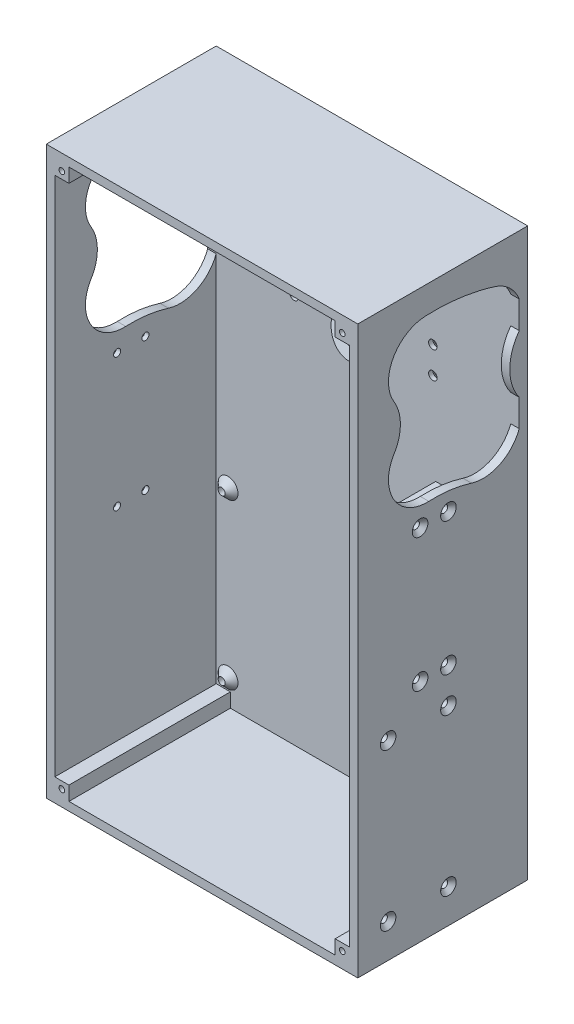
SolidWorks part; units mm, degrees
ref_plane "Płaszczyzna przednia" through (0, 0, 0) normal (0, 0, 1) x (1, 0, 0)
ref_plane "Płaszczyzna górna" through (0, 0, 0) normal (0, 1, 0) x (1, 0, 0)
ref_plane "Płaszczyzna prawa" through (0, 0, 0) normal (1, 0, 0) x (0, 0, -1)
sketch "Szkic1" plane through (0, 0, 0) normal (0, 1, 0) x (1, 0, 0)
  line L1 (0, 0) -> (110, 0)
  line L2 (0, 0) -> (0, 60)
  line L3 (0, 60) -> (110, 60)
  line L4 (110, 0) -> (110, 60)
  dimension "D1" = 110
  dimension "D2" = 60
extrude "Dodanie-wyciągnięcie1" add sketch "Szkic1" along normal blind 200
shell "Skorupa1" thickness 3 removed face at (55, 100, 0)
sketch "Szkic8" plane through (0, 0, -57) normal (0, 0, 1) x (1, 0, 0)
  line L0 (3, 197) -> (3, 192) construction
  line L1 (3, 197) -> (3, 3) construction
  line L2 (107, 197) -> (3, 197) construction
  line L3 (3, 192) -> (8, 192)
  line L4 (3, 192) -> (3, 197)
  line L5 (3, 197) -> (8, 197)
  line L6 (8, 192) -> (8, 197)
  circle A0 centre (5.5, 194.5) radius 1
  dimension "D2" = 2
  dimension "D1" = 5
sketch "Szkic12" plane through (0, 0, -57) normal (0, 0, 1) x (1, 0, 0)
  line L1 (107, 197) -> (102, 197)
  line L2 (107, 197) -> (107, 192)
  line L3 (107, 192) -> (102, 192)
  line L4 (102, 197) -> (102, 192)
  circle A0 centre (104.5, 194.5) radius 1
  dimension "D3" = 2
  dimension "D1" = 5
  dimension "D2" = 5
  dimension "D4" = 2.5
  dimension "D5" = 2.5
sketch "Szkic14" plane through (0, 0, -57) normal (0, 0, 1) x (1, 0, 0)
  line L1 (107, 3) -> (102, 3)
  line L2 (107, 3) -> (107, 8)
  line L3 (107, 8) -> (102, 8)
  line L4 (102, 3) -> (102, 8)
  circle A0 centre (104.5, 5.5) radius 1
  dimension "D2" = 2
  dimension "D3" = 2.5
  dimension "D1" = 5
  dimension "D4" = 2.5
sketch "Szkic16" plane through (0, 0, -57) normal (0, 0, 1) x (1, 0, 0)
  line L1 (3, 3) -> (8, 3)
  line L2 (3, 3) -> (3, 8)
  line L3 (3, 8) -> (8, 8)
  line L4 (8, 3) -> (8, 8)
  circle A0 centre (5.5, 5.5) radius 1
  dimension "D2" = 2
  dimension "D1" = 5
extrude "Dodanie-wyciągnięcie11" add sketch "Szkic16" along normal blind 57
extrude "Dodanie-wyciągnięcie14" add sketch "Szkic8" along normal blind 57
extrude "Dodanie-wyciągnięcie16" add sketch "Szkic12" along normal blind 57
extrude "Dodanie-wyciągnięcie17" add sketch "Szkic14" along normal blind 57
sketch "Szkic17" plane through (107, -8.5912, 0.3025) normal (-1, 0, 0) x (0, 0, 1)
  line L0 (-38.6312, 60.9912) -> (-38.6312, 16.5912) construction
  line L1 (-57.3012, 109.5912) -> (-38.6312, 109.5912)
  line L2 (-57.3012, 109.5912) -> (-57.3012, 117.1912)
  line L3 (-57.3012, 117.1912) -> (-38.6312, 117.1912)
  line L4 (-38.6312, 109.5912) -> (-38.6312, 117.1912)
  line L5 (-0.3025, 16.5912) -> (-57.3025, 16.5912) construction
  line L6 (-38.6312, 109.5912) -> (-38.6312, 16.5912) construction
  line L7 (-57.3012, 68.5912) -> (-38.6312, 68.5912)
  line L8 (-57.3012, 68.5912) -> (-57.3012, 60.9912)
  line L9 (-57.3012, 60.9912) -> (-38.6312, 60.9912)
  line L10 (-38.6312, 68.5912) -> (-38.6312, 60.9912)
  dimension "D1" = 18.67
  dimension "D2" = 7.6
  dimension "D3" = 44.4
  dimension "D4" = 93
  dimension "D5" = 18.67
  dimension "D6" = 7.6
extrude "Dodanie-wyciągnięcie18" add sketch "Szkic17" along normal blind 26.5
sketch "Szkic18" plane through (80.5, 0, 0) normal (-1, 0, 0) x (0, 0, 1)
  line L1 (-56.9987, 108.6) -> (-56.9987, 101) construction
  line L2 (-38.3287, 101) -> (-38.3287, 108.6) construction
  line L3 (-38.3287, 108.6) -> (-56.9987, 108.6) construction
  circle A0 centre (-42.3287, 105.6) radius 1.5
  circle A1 centre (-51.9787, 105.6) radius 1.5
  dimension "D1" = 3
  dimension "D2" = 3
  dimension "D3" = 3
  dimension "D4" = 5.02
  dimension "D5" = 3
  dimension "D6" = 4
extrude "Wytnij-wyciągnięcie2" cut sketch "Szkic18" against normal blind 5
sketch "Szkic19" plane through (80.5, 0, 0) normal (-1, 0, 0) x (0, 0, 1)
  line L0 (-56.9987, 52.4) -> (-38.3287, 52.4) construction
  line L4 (-38.3287, 52.4) -> (-38.3287, 60) construction
  line L5 (-56.9987, 60) -> (-56.9987, 52.4) construction
  circle A0 centre (-42.3287, 55.4) radius 1.5
  circle A1 centre (-51.9787, 55.4) radius 1.5
  dimension "D1" = 3
  dimension "D2" = 3
  dimension "D3" = 3
  dimension "D4" = 4
  dimension "D5" = 3
  dimension "D6" = 5.02
extrude "Wytnij-wyciągnięcie3" cut sketch "Szkic19" against normal blind 5
sketch "Szkic21" plane through (110, 0, 0) normal (1, 0, 0) x (0, 0, -1)
  line L0 (0, 0) -> (22, 0) construction
  line L1 (0, 0) -> (60, 0) construction
  line L2 (0, 0) -> (31, 0) construction
  line L5 (22, 126.68) -> (32, 126.68) construction
  line L7 (22, 126.68) -> (22, 79.68) construction
  line L8 (32, 126.68) -> (32, 79.68) construction
  line L9 (22, 79.68) -> (22, 0) construction
  line L10 (22, 79.68) -> (0, 79.68) construction
  line L11 (0, 200) -> (0, 0) construction
  circle A0 centre (22, 79.68) radius 1.25
  circle A1 centre (32, 79.68) radius 1.25
  circle A2 centre (22, 126.68) radius 1.25
  circle A3 centre (32, 126.68) radius 1.25
  dimension "D4" = 2.5
  dimension "D5" = 2.5
  dimension "D7" = 2.5
  dimension "D8" = 2.5
  dimension "D1" = 10
  dimension "D2" = 10
  dimension "D3" = 47
  dimension "D6" = 79.68
  dimension "D9" = 22
extrude "Wytnij-wyciągnięcie4" cut sketch "Szkic21" against normal blind 125
chamfer "Sfazowanie3" distance 1.5 angle 45 8 edges at (0, 79.68, -23.25) (0, 79.68, -33.25) (0, 126.68, -33.25) (0, 126.68, -23.25) (110, 126.68, -23.25) (110, 126.68, -33.25) (110, 79.68, -33.25) (110, 79.68, -23.25)
sketch "Szkic22" plane through (0, 108.6, 0) normal (0, 1, 0) x (1, 0, 0)
  line L0 (80.5, 38.3287) -> (98, 38.3287)
  line L1 (80.5, 38.3287) -> (107, 38.3287) construction
  line L2 (107, 38.3287) -> (107, 53.3287)
  line L3 (107, 38.3287) -> (107, 56.9987) construction
  line L4 (98, 38.3287) -> (107, 53.3287)
  line L5 (98, 38.3287) -> (107, 38.3287)
  dimension "D1" = 17.5
  dimension "D2" = 15
extrude "Wytnij-wyciągnięcie5" cut sketch "Szkic22" against normal blind 10 contours L5 L2 L4
sketch "Szkic24" plane through (0, 0, -57) normal (0, 0, 1) x (1, 0, 0)
  line L0 (8, 197) -> (102, 197) construction
  line L1 (55, 197) -> (55, 174.23) construction
  line L2 (55, 174.23) -> (55, 179.73) construction
  line L8 (55, 174.23) -> (48.524, 174.23) construction
  arc A2 (61.476, 174.23) -> (48.524, 174.23) centre (55, 179.73) ccw
  spline S0 degree 2 poles (48.524, 174.23) (55, 174.198) (61.476, 174.23) knots 0 0 0 1 1 1
  dimension "D3" = 16.9928
  dimension "D1" = 22.77
sketch "Szkic43" plane through (107, 0, 0) normal (-1, 0, 0) x (0, 0, 1)
  line L0 (-57, 139.4863) -> (-57, 149.0844)
  line L1 (-57, 179.13) -> (-57, 169.4506)
  line L2 (-57, 192) -> (-57, 8) construction
  line L4 (-57, 192) -> (-57, 179.13) construction
  arc A0 (-57, 179.13) -> (-48.3123, 187.2414) centre (-44.2889, 174.224) cw
  arc A2 (-23.8685, 190.4648) -> (-12.8025, 169.7853) centre (-24.4601, 176.8476) cw
  arc A3 (-12.8025, 169.7853) -> (-13.3589, 154.7507) centre (0.4315, 161.7679) ccw
  arc A4 (-13.3589, 154.7507) -> (-25.0675, 133.2257) centre (-24.4599, 146.8422) cw
  arc A5 (-25.0675, 133.2257) -> (-40.1456, 131.2527) centre (-27.0175, 89.5268) ccw
  arc A6 (-40.1456, 131.2527) -> (-57, 139.4863) centre (-44.2348, 144.2496) cw
  arc A7 (-57, 149.0844) -> (-57, 169.4506) centre (-70.8555, 159.2675) ccw
  spline S0 degree 2 poles (-48.3123, 187.2414) (-36.3724, 190.9917) (-23.8685, 190.4648) knots 0 0 0 1 1 1
  dimension "D2" = 13.63
  dimension "D3" = 13.63
  dimension "D4" = 15.4731
  dimension "D1" = 12.87
extrude "Wytnij-wyciągnięcie10" cut sketch "Szkic43" against normal blind 3 and the other way blind 125
sketch "Szkic48" plane through (0, 0, -57) normal (0, 0, 1) x (1, 0, 0)
  line L0 (36.9558, 197) -> (36.9558, 174.2) construction
  line L1 (8, 197) -> (102, 197) construction
  line L2 (36.9558, 174.2) -> (3, 174.2) construction
  line L3 (3, 192) -> (3, 8) construction
  line L4 (3, 174.2) -> (106.9534, 174.2) construction
  dimension "D1" = 22.8
revolve "Obrót1" add sketch "Szkic24" angle 20 about L4
sketch "Szkic49" plane through (0, 38.697, -106.3191) normal (0, -0.342, 0.9397) x (1, 0, 0)
  line L0 (54.9767, 144.1993) -> (54.9767, 149.6993) construction
  line L1 (3, 144.1993) -> (106.9534, 144.1993) construction
  circle A0 centre (54.9767, 149.6993) radius 5.5
  dimension "D1" = 5.5
extrude "Wytnij-wyciągnięcie11" cut sketch "Szkic49" against normal blind 3
sketch "Szkic50" plane through (0, 0, -57) normal (0, 0, 1) x (1, 0, 0)
  line L0 (54.9767, 174.2) -> (54.9767, 152.15) construction
  line L1 (3, 174.2) -> (106.9534, 174.2) construction
  line L2 (54.9767, 148.65) -> (54.9767, 143.15) construction
  line L3 (54.9767, 148.6644) -> (54.9767, 148.65) construction
  line L4 (54.9767, 148.6644) -> (54.9767, 148.7168) construction
  line L5 (54.9767, 148.7168) -> (3, 148.7168) construction
  line L6 (3, 192) -> (3, 8) construction
  line L7 (54.9767, 148.7168) -> (107, 148.7168) construction
  line L8 (107, 192) -> (107, 8) construction
  arc A1 (47.8528, 148.65) -> (62.1006, 148.65) centre (54.9767, 143.15) ccw
  spline S0 degree 2 poles (47.8528, 148.65) (54.9767, 148.6787) (62.1006, 148.65) knots 0 0 0 1 1 1
  dimension "D3" = 18
  dimension "D1" = 25.55
  dimension "D2" = 5.5
revolve "Obrót2" add sketch "Szkic50" angle 20 about L5
sketch "Szkic51" plane through (0, -0.9229, -2.5356) normal (0, 0.342, 0.9397) x (1, 0, 0)
  line L0 (54.9767, 159.1908) -> (54.9767, 153.6908) construction
  arc A0 (62.1006, 159.1764) -> (47.8528, 159.1764) centre (54.9767, -1606.2705) ccw construction
  circle A1 centre (54.9767, 153.6908) radius 5.5
  dimension "D1" = 5.5
extrude "Wytnij-wyciągnięcie12" cut sketch "Szkic51" against normal blind 3
sketch "Szkic52" plane through (0, 0, -57) normal (0, 0, 1) x (1, 0, 0)
  line L0 (30.5, 197) -> (30.5, 182.46) construction
  line L1 (102, 197) -> (8, 197) construction
  line L2 (3, 192) -> (3, 179.13) construction
  line L3 (30.5, 182.46) -> (30.5, 172.96) construction
  line L4 (30.5, 172.96) -> (30.5, 149.96) construction
  line L5 (30.5, 149.96) -> (30.5, 140.46) construction
  line L6 (30.5, 140.46) -> (79.5, 140.46) construction
  line L7 (79.5, 140.46) -> (79.5, 149.96) construction
  line L8 (79.5, 149.96) -> (79.5, 172.96) construction
  line L9 (79.5, 172.96) -> (79.5, 182.46) construction
  circle A0 centre (30.5, 182.46) radius 1.5
  circle A1 centre (30.5, 172.96) radius 1.5
  circle A2 centre (30.5, 149.96) radius 1.5
  circle A3 centre (30.5, 140.46) radius 1.5
  circle A4 centre (79.5, 140.46) radius 1.5
  circle A5 centre (79.5, 149.96) radius 1.5
  circle A6 centre (79.5, 172.96) radius 1.5
  circle A7 centre (79.5, 182.46) radius 1.5
  dimension "D3" = 3
  dimension "D10" = 3
  dimension "D11" = 3
  dimension "D12" = 3
  dimension "D13" = 3
  dimension "D14" = 3
  dimension "D15" = 3
  dimension "D16" = 3
  dimension "D1" = 14.54
  dimension "D2" = 27.5
  dimension "D4" = 9.5
  dimension "D5" = 23
  dimension "D6" = 9.5
  dimension "D7" = 9.5
  dimension "D8" = 23
  dimension "D9" = 9.5
  dimension "D17" = 49
  dimension "D18" = 14.54
extrude "Wytnij-wyciągnięcie13" cut sketch "Szkic52" against normal blind 3
chamfer "Sfazowanie4" distance 1.5 angle 45 8 edges at (81, 182.46, -60) (81, 172.96, -60) (81, 140.46, -60) (81, 149.96, -60) (32, 182.46, -60) (32, 172.96, -60) (32, 149.96, -60) (32, 140.46, -60)
ref_plane "Płaszczyzna1" through (104.5, 0, 0) normal (-1, 0, 0) x (0, 0, 1)
sketch "Szkic57" plane through (107, 0, 0) normal (-1, 0, 0) x (0, 0, 1)
  line L0 (0, 8) -> (-10.7, 8) construction
  line L1 (-10.7, 8) -> (-10.7, 11.95) construction
  circle A0 centre (-10.7, 11.95) radius 3.5
  dimension "D3" = 7
  dimension "D1" = 10.7
  dimension "D2" = 3.95
sketch "Szkic59" plane through (104.5, 0, 0) normal (-1, 0, 0) x (0, 0, 1)
  circle A0 centre (-10.7, 11.95) radius 1.25
  dimension "D1" = 2.5
sketch "Szkic60" plane through (107, 0, 0) normal (-1, 0, 0) x (0, 0, 1)
  line L0 (0, 68.5) -> (-10.7, 68.5) construction
  line L1 (0, 200) -> (0, 0) construction
  line L2 (-10.7, 68.5) -> (-10.7, 8.45) construction
  line L3 (-10.7, 68.5) -> (-10.7, 67.25) construction
  line L4 (0, 8) -> (-57, 8) construction
  circle A0 centre (-10.7, 67.25) radius 3.5
  dimension "D4" = 7
  dimension "D1" = 10.7
  dimension "D2" = 60.5
  dimension "D3" = 1.25
sketch "Szkic61" plane through (104.5, 0, 0) normal (-1, 0, 0) x (0, 0, 1)
  circle A0 centre (-10.7, 67.25) radius 1.25
  dimension "D1" = 2.5
sketch "Szkic62" plane through (107, 0, 0) normal (-1, 0, 0) x (0, 0, 1)
  line L0 (0, 68.5) -> (-32, 68.5) construction
  line L1 (0, 200) -> (0, 0) construction
  line L3 (-32, 68.5) -> (-32, 67.25) construction
  line L5 (-32, 67.25) -> (-32, 66) construction
  line L6 (0, 8) -> (-57, 8) construction
  circle A0 centre (-32, 67.25) radius 3.5
  dimension "D4" = 7
  dimension "D1" = 32
  dimension "D2" = 58
  dimension "D3" = 1.25
  dimension "D5" = 1.25
sketch "Szkic63" plane through (104.5, 0, 0) normal (-1, 0, 0) x (0, 0, 1)
  circle A0 centre (-32, 67.25) radius 1.25
  dimension "D1" = 2.5
sketch "Szkic64" plane through (107, 0, 0) normal (-1, 0, 0) x (0, 0, 1)
  line L0 (0, 11.95) -> (-32, 11.95) construction
  line L1 (0, 200) -> (0, 0) construction
  line L2 (0, 8) -> (-57, 8) construction
  circle A0 centre (-32, 11.95) radius 3.5
  dimension "D3" = 7
  dimension "D1" = 32
  dimension "D2" = 3.95
sketch "Szkic65" plane through (104.5, 0, 0) normal (-1, 0, 0) x (0, 0, 1)
  circle A0 centre (-32, 11.95) radius 1.25
  dimension "D1" = 2.5
sketch "Szkic68" plane through (0, 0, -57) normal (0, 0, 1) x (1, 0, 0)
  line L0 (7.2, 8) -> (7.2, 12) construction
  line L1 (8, 8) -> (3, 8) construction
  line L2 (7.2, 12) -> (3, 12) construction
  line L3 (3, 192) -> (3, 8) construction
  circle A0 centre (7.2, 12) radius 3.5
  dimension "D3" = 7
  dimension "D1" = 4
  dimension "D2" = 4.2
ref_plane "Płaszczyzna2" through (0, 0, -52.76) normal (0, 0, 1) x (1, 0, 0)
sketch "Szkic69" plane through (0, 0, -52.76) normal (0, 0, 1) x (1, 0, 0)
  circle A0 centre (7.2, 12) radius 1.2478
  dimension "D1" = 2.4955
loft "Wyciągnięcie po profilach6" add profiles "Szkic69", "Szkic68" connector at (6.1209, 12.6264, -52.76) connector at (10.5965, 12.8448, -57)
sketch "Szkic70" plane through (0, 0, -57) normal (0, 0, 1) x (1, 0, 0)
  line L0 (7.2, 12) -> (56.2, 12) construction
  circle A0 centre (56.2, 12) radius 3.5
  dimension "D2" = 7
  dimension "D1" = 49
sketch "Szkic71" plane through (0, 0, -52.76) normal (0, 0, 1) x (1, 0, 0)
  circle A0 centre (56.2, 12) radius 1.25
  dimension "D1" = 2.5
loft "Wyciągnięcie po profilach7" add profiles "Szkic71", "Szkic70" connector at (55.0585, 12.5094, -52.76) connector at (59.6718, 12.443, -57)
sketch "Szkic72" plane through (0, 0, -57) normal (0, 0, 1) x (1, 0, 0)
  line L0 (56.2, 12) -> (56.2, 70) construction
  circle A0 centre (56.2, 70) radius 3.5
  dimension "D2" = 7
  dimension "D1" = 58
sketch "Szkic73" plane through (0, 0, -52.76) normal (0, 0, 1) x (1, 0, 0)
  circle A0 centre (56.2, 70) radius 1.25
  dimension "D1" = 2.5
loft "Wyciągnięcie po profilach8" add profiles "Szkic73", "Szkic72" connector at (54.9931, 70.3253, -52.76) connector at (59.2586, 68.2985, -57)
sketch "Szkic75" plane through (0, 0, -57) normal (0, 0, 1) x (1, 0, 0)
  line L0 (7.2, 12) -> (7.2, 70) construction
  circle A0 centre (7.2, 70) radius 3.5
  dimension "D2" = 7
  dimension "D1" = 58
sketch "Szkic76" plane through (0, 0, -52.76) normal (0, 0, 1) x (1, 0, 0)
  circle A0 centre (7.2, 70) radius 1.25
  dimension "D1" = 2.5
loft "Wyciągnięcie po profilach9" add profiles "Szkic76", "Szkic75" connector at (6.0369, 70.458, -52.76) connector at (10.389, 71.4423, -57)
sketch "Szkic77" plane through (0, 0, -52.76) normal (0, 0, 1) x (1, 0, 0)
  circle A0 centre (7.2, 70) radius 1.25
  circle A1 centre (56.2, 70) radius 1.25
  circle A2 centre (56.2, 12) radius 1.25
  circle A3 centre (7.2, 12) radius 1.2478
extrude "Wytnij-wyciągnięcie16" cut sketch "Szkic77" against normal blind 4
extrude "Wytnij-wyciągnięcie17" cut sketch "Szkic61" against normal blind 10
extrude "Wytnij-wyciągnięcie18" cut sketch "Szkic63" against normal blind 10
extrude "Wytnij-wyciągnięcie19" cut sketch "Szkic65" against normal blind 10
extrude "Wytnij-wyciągnięcie20" cut sketch "Szkic59" against normal blind 10
chamfer "Sfazowanie5" distance 1.5 angle 45 4 edges at (110, 11.95, -9.45) (110, 67.25, -30.75) (110, 67.25, -9.45) (110, 11.95, -30.75)
